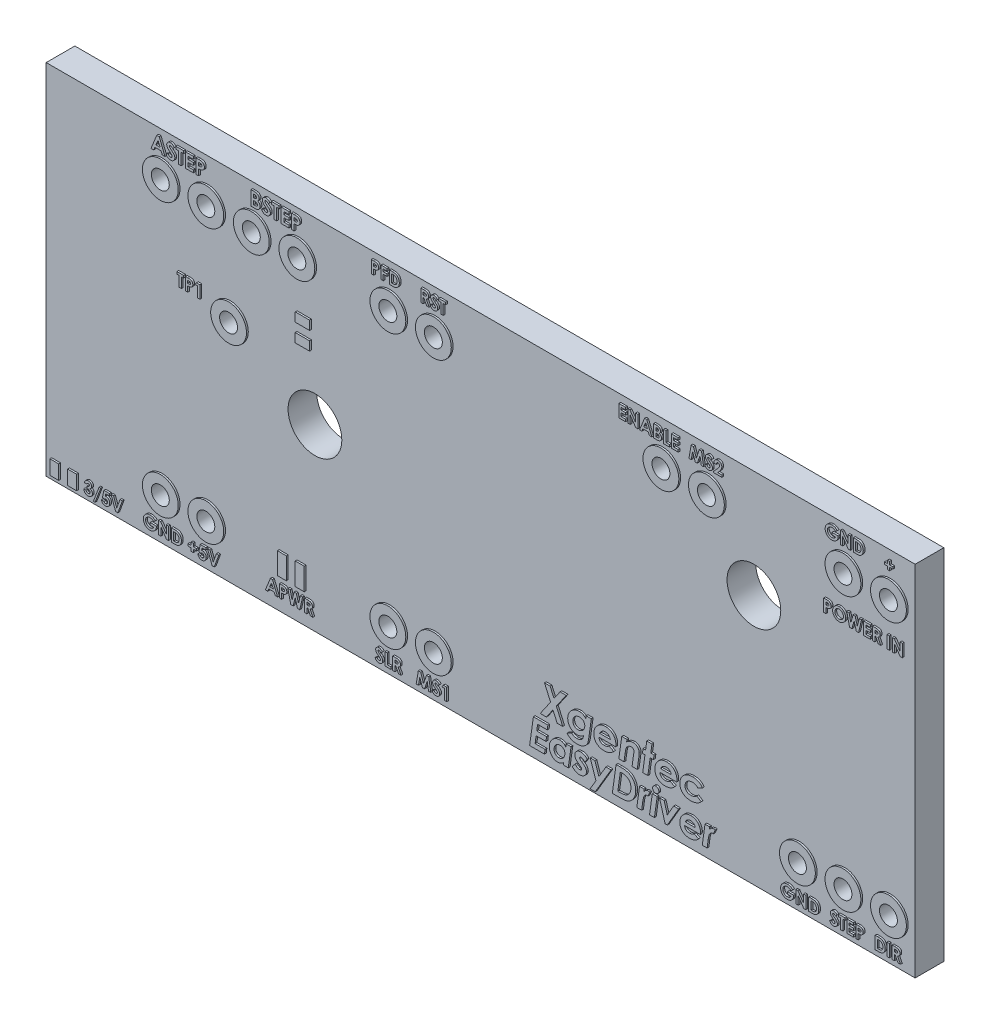
SolidWorks part; units mm, degrees
ref_plane "Front Plane" through (0, 0, 0) normal (0, 0, 1) x (1, 0, 0)
ref_plane "Top Plane" through (0, 0, 0) normal (0, 1, 0) x (1, 0, 0)
ref_plane "Right Plane" through (0, 0, 0) normal (1, 0, 0) x (0, 0, -1)
sketch "Sketch1" plane through (0, 0, 0) normal (0, 0, 1) x (1, 0, 0)
  line L1 (-24.25, 10) -> (24.25, 10)
  line L2 (-24.25, 10) -> (-24.25, -10)
  line L3 (-24.25, -10) -> (24.25, -10)
  line L4 (24.25, 10) -> (24.25, -10)
  line L5 (-24.25, 10) -> (24.25, -10) construction
  line L6 (-24.25, -10) -> (24.25, 10) construction
  circle A0 centre (-9.25, 0) radius 1.5
  circle A1 centre (15.25, 4) radius 1.5
  point P0 (0, 0)
  dimension "D3" = 3
  dimension "D4" = 3
  dimension "D1" = 48.5
  dimension "D2" = 20
  dimension "D5" = 15
  dimension "D6" = 9
  dimension "D7" = 6
extrude "Boss-Extrude1" add sketch "Sketch1" along normal blind 1.6
sketch "Sketch2" plane through (0, 0, 1.6) normal (0, 0, 1) x (1, 0, 0)
  line L0 (0, -10) -> (0, 10) construction
  line L1 (-24.25, -10) -> (24.25, -10) construction
  line L2 (24.25, 10) -> (-24.25, 10) construction
  circle A0 centre (-2.54, 7.625) radius 1
  circle A1 centre (-2.54, -7.625) radius 1
  circle A2 centre (-5.08, 7.625) radius 1
  circle A3 centre (-5.08, -7.625) radius 1
  circle A6 centre (-10.16, 7.625) radius 1
  circle A8 centre (-12.7, 7.625) radius 1
  circle A10 centre (-15.24, 7.625) radius 1
  circle A11 centre (-15.24, -7.625) radius 1
  circle A12 centre (-17.78, 7.625) radius 1
  circle A13 centre (-17.78, -7.625) radius 1
  circle A18 centre (-20.32, 7.625) radius 1 [skipped]
  circle A19 centre (-22.86, 7.625) radius 1 [skipped]
  circle A20 centre (-7.62, 7.625) radius 1 [skipped]
  circle A21 centre (-20.32, -7.625) radius 1 [skipped]
  circle A22 centre (-22.86, -7.625) radius 1 [skipped]
  circle A23 centre (-7.62, -7.625) radius 1 [skipped]
  circle A24 centre (-10.16, -7.625) radius 1 [skipped]
  circle A25 centre (-12.7, -7.625) radius 1 [skipped]
  dimension "D5" = 2
  dimension "D6" = 2
  dimension "D1" = 2.54
  dimension "D2" = 2.54
  dimension "D3" = 15.25
  dimension "D4" = 7.625
  dimension "D7" = 9
extrude "Boss-Extrude2" add sketch "Sketch2" along normal blind 0.1 and the other way blind 1.7
sketch "Sketch3" plane through (0, 0, 1.6) normal (0, 0, 1) x (1, 0, 0)
  line L0 (0, -10) -> (0, 10) construction
  line L1 (-24.25, -10) -> (24.25, -10) construction
  line L2 (24.25, 10) -> (-24.25, 10) construction
  circle A0 centre (22.86, 7.625) radius 1
  circle A1 centre (22.86, -7.625) radius 1
  circle A2 centre (20.32, 7.625) radius 1
  circle A3 centre (20.32, -7.625) radius 1
  circle A5 centre (17.78, -7.625) radius 1
  circle A8 centre (12.7, 7.625) radius 1
  circle A10 centre (10.16, 7.625) radius 1
  circle A18 centre (17.78, 7.625) radius 1 [skipped]
  circle A19 centre (15.24, 7.625) radius 1 [skipped]
  circle A20 centre (7.62, 7.625) radius 1 [skipped]
  circle A21 centre (5.08, 7.625) radius 1 [skipped]
  circle A22 centre (2.54, 7.625) radius 1 [skipped]
  circle A23 centre (15.24, -7.625) radius 1 [skipped]
  circle A24 centre (12.7, -7.625) radius 1 [skipped]
  circle A25 centre (10.16, -7.625) radius 1 [skipped]
  circle A26 centre (7.62, -7.625) radius 1 [skipped]
  circle A27 centre (5.08, -7.625) radius 1 [skipped]
  circle A28 centre (2.54, -7.625) radius 1 [skipped]
  dimension "D3" = 2
  dimension "D4" = 2
  dimension "D1" = 15.25
  dimension "D2" = 22.86
  dimension "D5" = 22.86
  dimension "D6" = 9
extrude "Boss-Extrude3" add sketch "Sketch3" along normal blind 0.1 and the other way blind 1.7
sketch "Sketch4" plane through (0, 0, 1.7) normal (0, 0, 1) x (1, 0, 0)
  circle A0 centre (22.86, 7.625) radius 0.5
  circle A1 centre (22.86, -7.625) radius 0.5
  circle A2 centre (20.32, 7.625) radius 0.5
  circle A3 centre (20.32, -7.625) radius 0.5
  circle A5 centre (17.78, -7.625) radius 0.5
  circle A8 centre (12.7, 7.625) radius 0.5
  circle A10 centre (10.16, 7.625) radius 0.5
  circle A20 centre (-2.54, 7.625) radius 0.5
  circle A21 centre (-2.54, -7.625) radius 0.5
  circle A22 centre (-5.08, 7.625) radius 0.5
  circle A23 centre (-5.08, -7.625) radius 0.5
  circle A26 centre (-10.16, 7.625) radius 0.5
  circle A28 centre (-12.7, 7.625) radius 0.5
  circle A30 centre (-15.24, 7.625) radius 0.5
  circle A31 centre (-15.24, -7.625) radius 0.5
  circle A32 centre (-17.78, 7.625) radius 0.5
  circle A33 centre (-17.78, -7.625) radius 0.5
  circle A38 centre (-20.32, -7.625) radius 0.5 [skipped]
  circle A39 centre (-22.86, -7.625) radius 0.5 [skipped]
  circle A40 centre (-20.32, 7.625) radius 0.5 [skipped]
  circle A41 centre (-22.86, 7.625) radius 0.5 [skipped]
  circle A42 centre (-7.62, 7.625) radius 0.5 [skipped]
  circle A43 centre (7.62, 7.625) radius 0.5 [skipped]
  circle A44 centre (5.08, 7.625) radius 0.5 [skipped]
  circle A45 centre (2.54, 7.625) radius 0.5 [skipped]
  circle A46 centre (0, 7.625) radius 0.5 [skipped]
  circle A47 centre (17.78, 7.625) radius 0.5 [skipped]
  circle A48 centre (15.24, 7.625) radius 0.5 [skipped]
  circle A49 centre (15.24, -7.625) radius 0.5 [skipped]
  circle A50 centre (12.7, -7.625) radius 0.5 [skipped]
  circle A51 centre (10.16, -7.625) radius 0.5 [skipped]
  circle A52 centre (7.62, -7.625) radius 0.5 [skipped]
  circle A53 centre (5.08, -7.625) radius 0.5 [skipped]
  circle A54 centre (2.54, -7.625) radius 0.5 [skipped]
  circle A55 centre (0, -7.625) radius 0.5 [skipped]
  circle A56 centre (-7.62, -7.625) radius 0.5 [skipped]
  circle A57 centre (-10.16, -7.625) radius 0.5 [skipped]
  circle A58 centre (-12.7, -7.625) radius 0.5 [skipped]
  dimension "D1" = 1
  dimension "D2" = 1
  dimension "D3" = 19
extrude "Cut-Extrude1" cut sketch "Sketch4" against normal blind 2
sketch "Sketch5" plane through (0, 0, 1.6) normal (0, 0, 1) x (1, 0, 0)
  circle A0 centre (-13.97, 2.625) radius 1
  circle A1 centre (-15.24, 7.625) radius 1 construction
  circle A2 centre (-12.7, 7.625) radius 1 construction
  dimension "D1" = 2
  dimension "D2" = 5
  dimension "D3" = 1.27
extrude "Boss-Extrude4" add sketch "Sketch5" along normal blind 0.1 and the other way blind 1.7
sketch "Sketch6" plane through (0, 0, 1.7) normal (0, 0, 1) x (1, 0, 0)
  circle A0 centre (-13.97, 2.625) radius 0.5
  dimension "D1" = 1
extrude "Cut-Extrude2" cut sketch "Sketch6" against normal blind 2
sketch "Sketch7" plane through (0, 0, 1.6) normal (0, 0, 1) x (1, 0, 0)
  line L0 (-24.25, 10) -> (-24.25, -10) construction
  line L1 (-23.95, -8.95) -> (-23.45, -8.95)
  line L2 (-23.95, -8.95) -> (-23.95, -9.75)
  line L3 (-23.95, -9.75) -> (-23.45, -9.75)
  line L4 (-23.45, -8.95) -> (-23.45, -9.75)
  line L5 (-22.95, -8.9499) -> (-22.45, -8.9499)
  line L6 (-22.95, -8.9499) -> (-22.95, -9.7499)
  line L7 (-22.95, -9.7499) -> (-22.45, -9.7499)
  line L8 (-22.45, -8.9499) -> (-22.45, -9.7499)
  line L9 (-24.25, -10) -> (24.25, -10) construction
  line L10 (24.25, 10) -> (-24.25, 10) construction
  line L11 (-11.25, -7.042) -> (-10.75, -7.042)
  line L12 (-11.25, -7.042) -> (-11.25, -8.25)
  line L13 (-11.25, -8.25) -> (-10.75, -8.25)
  line L14 (-10.75, -7.042) -> (-10.75, -8.25)
  line L15 (-10.25, -7.042) -> (-9.75, -7.042)
  line L16 (-10.25, -7.042) -> (-10.25, -8.2823)
  line L17 (-10.25, -8.2823) -> (-9.75, -8.2823)
  line L18 (-9.75, -7.042) -> (-9.75, -8.2823)
  line L19 (-10.25, 5) -> (-9.45, 5)
  line L20 (-10.25, 5) -> (-10.25, 4.5)
  line L21 (-10.25, 4.5) -> (-9.45, 4.5)
  line L22 (-9.45, 5) -> (-9.45, 4.5)
  line L23 (-10.25, 4) -> (-9.45, 4)
  line L24 (-10.25, 4) -> (-10.25, 3.5)
  line L25 (-10.25, 3.5) -> (-9.45, 3.5)
  line L26 (-9.45, 4) -> (-9.45, 3.5)
  dimension "D1" = 0.5
  dimension "D2" = 0.5
  dimension "D3" = 0.8
  dimension "D4" = 0.8
  dimension "D5" = 0.5
  dimension "D6" = 0.3
  dimension "D7" = 0.25
  dimension "D8" = 0.5
  dimension "D9" = 0.5
  dimension "D10" = 0.5
  dimension "D11" = 13
  dimension "D12" = 1.75
  dimension "D13" = 0.5
  dimension "D14" = 0.5
  dimension "D15" = 0.5
  dimension "D16" = 0.8
  dimension "D17" = 0.8
  dimension "D18" = 5
  dimension "D19" = 14
  dimension "D20" = 0
extrude "Boss-Extrude5" add sketch "Sketch7" along normal blind 0.1
sketch "Sketch8" plane through (0, 0, 1.6) normal (0, 0, 1) x (1, 0, 0)
  text T0 "3/5V" font "Century Gothic" height 0.7
  text T1 "GND +5V" font "Century Gothic" height 0.7
  text T2 "APWR" font "Century Gothic" height 0.7
  text T3 "SLR   MS1" font "Century Gothic" height 0.7
  text T4 "GND  STEP  DIR" font "Century Gothic" height 0.7
  text T5 "GND    +" font "Century Gothic" height 0.7
  text T6 "ENABLE  MS2" font "Century Gothic" height 0.7
  text T7 "POWER IN" font "Century Gothic" height 0.7
  text T8 "PFD    RST" font "Century Gothic" height 0.7
  text T9 "ASTEP        BSTEP" font "Century Gothic" height 0.8
  text T10 "TP1" font "Century Gothic" height 0.7
  text T11 "<i>Xgentec</i>" font "Century Gothic" height 1.6
  text T12 "<i>EasyDriver</i>" font "Century Gothic" height 1.5
extrude "Boss-Extrude6" add sketch "Sketch8" along normal blind 0.1
